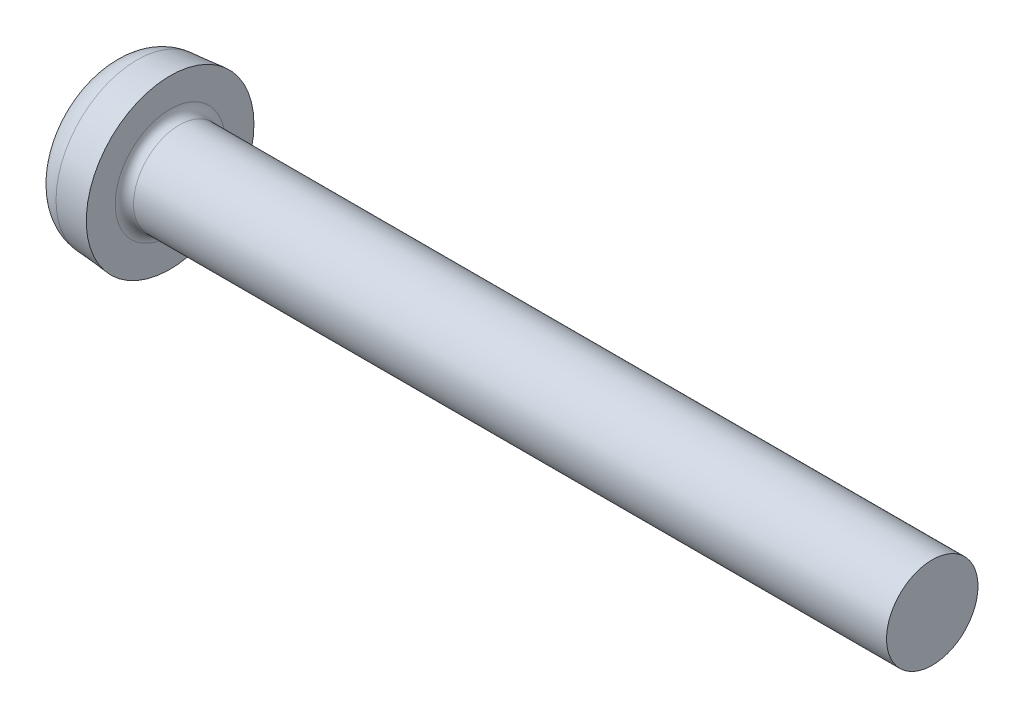
SolidWorks part; units mm, degrees
ref_plane "Front" through (0, 0, 0) normal (0, 0, 1) x (1, 0, 0)
ref_plane "Top" through (0, 0, 0) normal (0, 1, 0) x (1, 0, 0)
ref_plane "Right" through (0, 0, 0) normal (1, 0, 0) x (0, 0, -1)
sketch "Sketch1" plane through (0, 0, 0) normal (0, 0, 1) x (1, 0, 0)
  line L0 (27, 1.5) -> (3, 1.5)
  line L1 (2, 1.8) -> (2, 2.75)
  line L2 (2, 2.75) -> (0, 2.575)
  line L3 (3, 1.5) -> (2.3, 1.5)
  line L4 (27, 1.5) -> (27, 0)
  line L5 (4.5158, 0) -> (-13.5157, 0) construction
  line L6 (27, 0) -> (0, 0)
  line L7 (0, 0) -> (0, 2.575)
  arc A1 (2, 1.8) -> (2.3, 1.5) centre (2.3, 1.8) ccw
  dimension "D2" = 95
revolve "Base" add sketch "Sketch1" angle 360 about L5
cosmetic thread "ThreadCosmetic1" [suppressed] parameters "bb"=25
sketch "Sketch6" plane through (0, 0, 0) normal (1, 0, 0) x (0, 0, -1)
  line L0 (-1.9271, 0) -> (2.0512, 0) construction
  line L1 (0, 1.8651) -> (0, -2.0207) construction
  line L2 (0.35, 0.35) -> (0.35, 1.75)
  line L3 (0.35, 1.75) -> (-0.35, 1.75)
  line L4 (-0.35, 0.35) -> (-0.35, 1.75)
  line L5 (0.35, 0.35) -> (1.75, 0.35)
  line L6 (1.75, 0.35) -> (1.75, -0.35)
  line L7 (-1.75, 0.35) -> (-1.75, -0.35)
  line L8 (-0.35, 0.35) -> (-1.75, 0.35)
  line L9 (-0.35, -0.35) -> (-1.75, -0.35)
  line L10 (0.35, -0.35) -> (1.75, -0.35)
  line L11 (-0.35, -0.35) -> (-0.35, -1.75)
  line L12 (0.35, -1.75) -> (-0.35, -1.75)
  line L13 (0.35, -0.35) -> (0.35, -1.75)
  point P16 (-1.75, 0)
  point P17 (1.75, 0)
extrude "CrossRecess" cut sketch "Sketch6" along normal blind 2
fillet "Fillet5" radius 0.3 4 edges at (1, -0.35, 0.35) (1, -0.35, -0.35) (1, 0.35, 0.35) (1, 0.35, -0.35)
sketch "Sketch8" [suppressed] plane through (0, 0, 0) normal (0, 0, 1) x (1, 0, 0)
  line L0 (12, 4) -> (8.2, 3.5)
  line L1 (8.2, 3.5) -> (5, 3.5)
  line L3 (50, -4) -> (50, 4) construction
  line L4 (5, -6.5) -> (5, 6.5) construction
  line L6 (5, 3.5) -> (5, 14)
  line L7 (5, 14) -> (12, 14)
  line L8 (12, 14) -> (12, 4)
  line L9 (52.4753, 0) -> (42.9594, 0) construction
fillet "HeadFillet" radius 1 1 edges at (0, 0, -2.575)
draft "Draft1" type of draft neutral plane draft angle 20 faces to draft 4 face at (1.004, -0.0875, 1.75) face at (1.004, -1.75, -0.0875) face at (1.004, 0.0875, -1.75) face at (1.004, 1.75, 0.0875) neutral plane through (0, 0, 0) neutral plane normal (-1, 0, 0) parameters "D1"=20
sketch "Sketch7" plane through (0, 0, 0) normal (1, 0, 0) x (0, 0, -1)
  line L0 (-8.3217, 0) -> (7.4212, 0) construction
  line L1 (0, 7.4989) -> (0, -7.9646) construction
  line L2 (0, 0) -> (6.8599, 6.8599) construction
  line L3 (1.2374, 1.2374) -> (0, 0.6604)
  line L4 (0, 0) -> (-6.8599, 6.8599) construction
  line L5 (1.2374, 1.2374) -> (0.6604, 0)
  line L6 (1.2374, -1.2374) -> (0, -0.6604)
  line L7 (1.2374, -1.2374) -> (0.6604, 0)
  line L8 (-1.2374, -1.2374) -> (0, -0.6604)
  line L9 (-1.2374, -1.2374) -> (-0.6604, 0)
  line L10 (-1.2374, 1.2374) -> (0, 0.6604)
  line L11 (-1.2374, 1.2374) -> (-0.6604, 0)
  dimension "D2" = 20
extrude "Cut-Extrude3" [suppressed] cut sketch "Sketch7" along normal blind 10 draft 20
sketch "Sketch10" plane through (0, 0, 0) normal (0, 0, 1) x (1, 0, 0)
  line L0 (27, 1.2657) -> (27.1353, 1.5)
  line L1 (27.1353, 1.5) -> (27.1353, 1.7705)
  line L2 (27.1353, 1.7705) -> (26.8648, 1.7705)
  line L3 (26.8648, 1.7705) -> (26.8648, 1.5)
  line L4 (26.8648, 1.5) -> (27, 1.2657)
  line L5 (27, 1.5) -> (3, 1.5) construction
  line L6 (27, 1.5) -> (27, 0) construction
  line L7 (0, 0) -> (57.111, 0) construction
revolve "Cut-Revolve10" [suppressed] cut sketch "Sketch10" angle 360 about L7
pattern_linear "LPattern10" [suppressed] count 77 spacing 0.3246 along (-1, 0, 0) of bodies 107
equation "\"D1@Sketch6\" = \"m@Sketch6\" / 5"
equation "\"D1@Sketch8\" = \"d@Sketch8\" + 20"
equation "\"D1@Sketch10\" =  ( \"d@Sketch1\" - \"THD_MINOR@ThreadCosmetic1\" )  / 2"
equation "\"D3@LPattern10\" = \"D1@Sketch10\" * 1.2"
equation "\"D1@LPattern10\" = \"bb@ThreadCosmetic1\" / \"D3@LPattern10\" "
